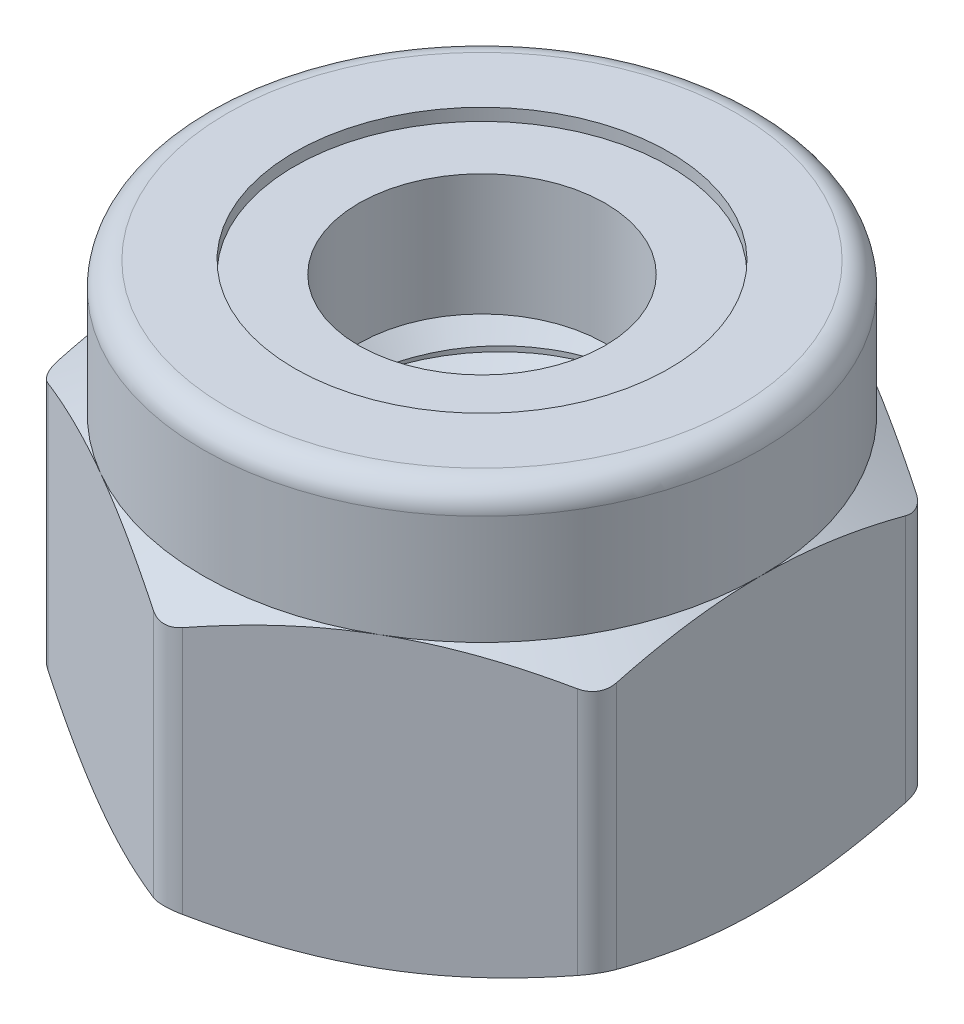
SolidWorks part; units mm, degrees
ref_plane "Front Plane" through (0, 0, 0) normal (0, 0, 1) x (1, 0, 0)
ref_plane "Top Plane" through (0, 0, 0) normal (0, 1, 0) x (1, 0, 0)
ref_plane "Right Plane" through (0, 0, 0) normal (1, 0, 0) x (0, 0, -1)
sketch "Sketch1" plane through (0, 0, 0) normal (0, 0, 1) x (1, 0, 0)
  line L0 (-3.5, -2.65) -> (3.5, -2.65) construction
  line L1 (-3.5, -2.65) -> (-3.5, 0.9742) construction
  line L2 (-3.5, 0.9742) -> (3.5, 0.9742) construction
  line L7 (3.5, 0.9742) -> (3.5, -2.65) construction
  line L8 (0, 2.65) -> (0, -2.65) construction
  line L9 (-2, 2.65) -> (-2, -2.65) construction
  line L10 (2, 2.65) -> (2, -2.65) construction
  line L11 (-2, 2.65) -> (2, 2.65) construction
  line L14 (3.5, -2.65) -> (4.0406, -2.3379) construction
  line L15 (3.5, 0.9742) -> (3.5, 2.65) construction
  line L16 (3.5, 2.65) -> (2, 2.65) construction
  line L17 (4.0406, -2.3379) -> (4.0406, 0.6621) construction
  line L18 (-3.5, 0.9742) -> (-3.5, 2.65) construction
  line L19 (-3.5, 2.65) -> (-2, 2.65) construction
  line L20 (4.0406, 0.6621) -> (3.5, 0.9742) construction
  line L21 (-2, -2.65) -> (-2, -3.2625) construction
  line L22 (-2, -3.2625) -> (-1.4696, -2.9563) construction
  line L23 (-1.4696, -2.9563) -> (-2, -2.65) construction
  line L24 (-2.0758, -2.6063) -> (-2.0758, -3.3063) construction
  line L25 (-2.0758, -2.6063) -> (-2, -2.65) construction
  line L26 (-2, -3.2625) -> (-2.0758, -3.3063) construction
  line L27 (-1.5453, -2.9125) -> (-1.5453, -3) construction
  line L28 (-2, -2.9563) -> (-2.0758, -2.9563) construction
  line L29 (-1.5453, -2.9563) -> (-1.4696, -2.9563) construction
  dimension "Width | s" = 7
  dimension "Thread Diameter" = 4
  dimension "Height | h" = 5.3
  dimension "D1" = 8.0811
  dimension "D2" = 30
  dimension "Flats Height" = 3
  dimension "Thread Pitch" = 0.7
  dimension "D4" = 0.0875
sketch "Sketch2" plane through (0, 0, 0) normal (0, 1, 0) x (1, 0, 0)
  line L0 (0, 0) -> (1.75, 3.0311) construction
  line L1 (3.5, 2.0207) -> (0, 4.0415)
  line L2 (0, 4.0415) -> (-3.5, 2.0207)
  line L3 (-3.5, 2.0207) -> (-3.5, -2.0207)
  line L4 (-3.5, -2.0207) -> (0, -4.0415)
  line L5 (0, -4.0415) -> (3.5, -2.0207)
  line L6 (3.5, -2.0207) -> (3.5, 2.0207)
  line L7 (0, 0) -> (3.5, 2.0207) construction
  circle A0 centre (0, 0) radius 3.5 construction
  circle A1 centre (0, 0) radius 4.0415 construction
extrude "Boss-Extrude1" add sketch "Sketch2" against normal up to vertex (2.65 mm away) from vertex up to point (3.5, -2.65, 0) starting at point (3.5, 0.9742, 0)
sketch "Sketch3" plane through (0, 0, 0) normal (0, 0, 1) x (1, 0, 0)
  line L3 (2, 1.8402) -> (4.0506, 0.6563)
  line L4 (2, 2.65) -> (2, -2.65) construction
  line L5 (2, -3.516) -> (4.0506, -2.3321)
  line L6 (4.0506, -2.3321) -> (4.0506, -3.516)
  line L7 (4.0506, -3.516) -> (2, -3.516)
  line L8 (2, 1.8402) -> (4.0506, 1.8402)
  line L10 (4.0506, 0.6563) -> (4.0506, 1.8402)
  dimension "D1" = 0.01
revolve "Cut-Revolve1" cut sketch "Sketch3" angle 360 about L8
fillet "Fillet1" radius 0.3604 6 edges at (-3.5, -0.8379, -2.0207) (-3.5, -0.8379, 2.0207) (0, -0.8379, 4.0415) (0, -0.8379, -4.0415) (3.5, -0.8379, -2.0207) (3.5, -0.8379, 2.0207)
sketch "Sketch5" plane through (0, 0, 0) normal (0, 0, 1) x (1, 0, 0)
  line L0 (-2.35, -2.65) -> (-2, -2.3)
  line L1 (-3.5, -2.65) -> (3.5, -2.65) construction
  line L2 (-2, 2.65) -> (-2, -2.65) construction
  line L3 (-2, -2.3) -> (-2, 0.6242)
  line L4 (-2, 0.6242) -> (-2.35, 0.9742)
  line L5 (-3.5, 0.9742) -> (3.5, 0.9742) construction
  line L6 (-2.35, 0.9742) -> (0, 0.9742)
  line L7 (0, 0.9742) -> (0, -2.65)
  line L8 (0, -2.65) -> (-2.35, -2.65)
  line L9 (0, 2.65) -> (0, -2.65) construction
  dimension "D1" = 45
  dimension "D2" = 0.35
revolve "Cut-Revolve2" cut sketch "Sketch5" angle 360 about L8
sketch "Sketch4" plane through (0, 0, 0) normal (0, 0, 1) x (1, 0, 0)
  line L0 (-2.35, 2.65) -> (-3.1938, 2.65)
  line L1 (-3.5, 2.65) -> (-2, 2.65) construction
  line L2 (-3.5, 2.3438) -> (-3.5, 0.9742)
  line L4 (-3.1938, 2.65) -> (-3.1938, 2.3438) construction
  line L5 (-1.7348, -2.8031) -> (-1.7348, -3.1094) construction
  line L6 (-1.4696, -2.9563) -> (-2, -2.65) construction
  line L7 (-2, -3.2625) -> (-1.4696, -2.9563) construction
  line L8 (-3.5, 0.9742) -> (-3.3469, 0.9742)
  line L10 (-2.35, 2.4969) -> (-2.35, 2.65)
  line L11 (-2.35, 2.4969) -> (-3.1938, 2.4969)
  line L12 (-3.3469, 2.3438) -> (-3.3469, 0.9742)
  arc A0 (-3.5, 2.3438) -> (-3.1938, 2.65) centre (-3.1938, 2.3438) cw
  arc A1 (-3.1938, 2.4969) -> (-3.3469, 2.3438) centre (-3.1938, 2.3438) ccw
revolve "Revolve1" add sketch "Sketch4" angle 360 about L8
sketch "Sketch6" plane through (0, 0, 0) normal (0, 0, 1) x (1, 0, 0)
  line L0 (-3.5, 0.9742) -> (3.5, 0.9742) construction
  line L1 (-3.1938, 2.4969) -> (-1.5453, 2.4969)
  line L2 (-3.3469, 2.3438) -> (-3.3469, 0.9742)
  line L3 (-3.3469, 0.9742) -> (-1.5453, 0.9742)
  line L4 (-1.5453, 2.4969) -> (-1.5453, 0.9742)
  arc A0 (-3.1938, 2.4969) -> (-3.3469, 2.3438) centre (-3.1937, 2.3438) ccw
revolve "Revolve2" add sketch "Sketch6" angle 360 about L8
sketch "Sketch7" plane through (0, -2.65, 0) normal (0, 1, 0) x (-1, 0, 0)
  line L0 (2, 0) -> (-2, 0) construction
  line L1 (0, 0) -> (-1.4142, -1.4142) construction
  circle A0 centre (0, 0) radius 2
  point P7 (-1.4142, -1.4142)
  dimension "D1" = 225
curve "Helix/Spiral1" pitch 0.7 height 5.3 radius 2 left hand yes centre (0, -2.65, 0) axis (0, 1, 0) start towards (0, 0, 1)
sketch "Sketch8" plane through (0, 0, 0) normal (0, 0, 1) x (1, 0, 0)
  line L0 (-2.0379, -2.6281) -> (-2.0379, -3.2844)
  line L1 (-2.0758, -2.6063) -> (-2, -2.65) construction
  line L2 (-2, -3.2625) -> (-2.0758, -3.3063) construction
  line L3 (-2.0379, -3.2844) -> (-1.5453, -3)
  line L4 (-1.5453, -3) -> (-1.5453, -2.9125)
  line L5 (-1.5453, -2.9125) -> (-2.0379, -2.6281)
sweep "Sweep1" add profiles "Sketch8" path "Helix/Spiral1"
sketch "Sketch9" plane through (0, 0, 0) normal (0, 0, 1) x (1, 0, 0)
  line L0 (-2.35, 2.8031) -> (-2.35, 0.9742)
  line L1 (-2.35, 0.9742) -> (-1.4696, 0.0937)
  line L2 (-1.4696, 0.0937) -> (-1.4696, 2.8031)
  line L4 (-1.4696, 2.8031) -> (-2.35, 2.8031)
  line L5 (-1.4696, -1.7696) -> (-2.35, -2.65)
  line L6 (-2.35, -2.65) -> (-2.35, -3.3063)
  line L7 (-2.35, -3.3063) -> (-1.4696, -3.3063)
  line L8 (-1.4696, -3.3063) -> (-1.4696, -1.7696)
  line L9 (-1.9098, 2.8031) -> (-1.9098, 2.65) construction
  line L10 (-2, 2.65) -> (2, 2.65) construction
  line L12 (-2.35, 2.4969) -> (-2.35, 2.65) construction
revolve "Cut-Revolve3" cut sketch "Sketch9" angle 360 about L8
equation "\"D1@Sketch1\"=\"Width | s@Sketch1\"*(1.15+.04/9)"
equation "\"D1@Fillet1\"=(\"D1@Sketch1\"-\"Width | s@Sketch1\")/3"
equation "\"D4@Sketch1\" = \"Thread Pitch@Sketch1\" / 8"
equation "\"D2@Sketch5\"=\"Thread Pitch@Sketch1\"*.5"
equation "\"D3@Helix/Spiral1\"=\"Height | h@Sketch1\""
equation "\"D4@Helix/Spiral1\"=\"Thread Pitch@Sketch1\""
